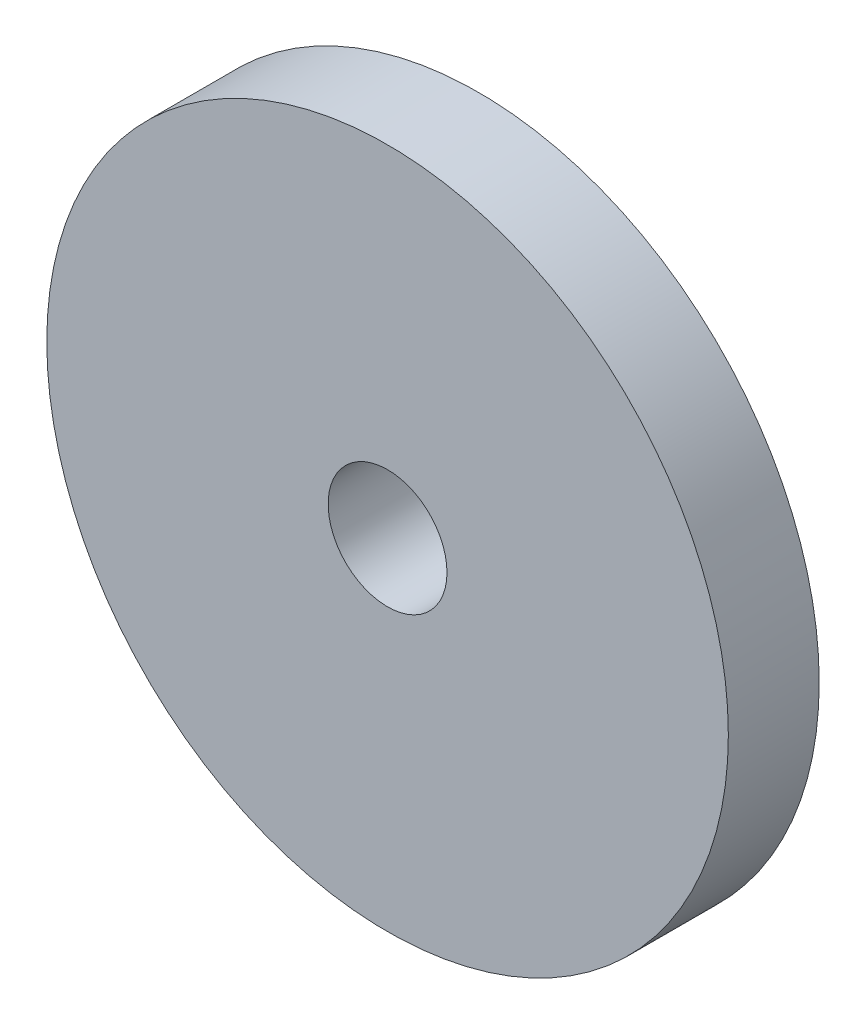
SolidWorks part; units mm, degrees
ref_plane "前视基准面" through (0, 0, 0) normal (0, 0, 1) x (1, 0, 0)
ref_plane "上视基准面" through (0, 0, 0) normal (0, 1, 0) x (1, 0, 0)
ref_plane "右视基准面" through (0, 0, 0) normal (1, 0, 0) x (0, 0, -1)
sketch "草图1" plane through (0, 0, 0) normal (0, 0, 1) x (1, 0, 0)
  circle A0 centre (0, 0) radius 150
  circle A1 centre (0, 0) radius 75
  circle A2 centre (0, 0) radius 38.1
  dimension "D" = 300
  dimension "P" = 150
  dimension "H" = 76.2
sketch "草图2" plane through (0, 0, 0) normal (0, 1, 0) x (1, 0, 0)
  line L0 (0, 11.2412) -> (0, -69.6952) construction
  point P3 (0, -40)
  point P4 (0, -20)
  dimension "F" = 20
  dimension "T" = 40
extrude "凸台-拉伸1" add sketch "草图1" along normal up to vertex (40 mm away) contours A0 A1 | A1 A2 region at (-145.7574, 0, 0) region at (-72.8787, 0, 0) up to point (0, 0, 40)
extrude "切除-拉伸1" cut sketch "草图1<4>" along normal up to vertex (20 mm away) contours A1 A2 region at (-72.8787, 0, 0) up to point (0, 0, 20)
sketch "草图1<4>" plane through (0, 0, 0) normal (0, 0, 1) x (1, 0, 0) same geometry as "草图1"
fillet "圆角1" radius 3.2 1 edges at (75, 0, 20)
scale "缩放比例1" scale about centroid uniform scaling yes scale factor 0.4
sketch "草图3" plane through (0, 0, 28.6598) normal (0, 0, 1) x (1, 0, 0)
  circle A0 centre (0, 0) radius 10.4619
  circle A1 centre (0, 0) radius 15.8137
extrude "凸台-拉伸2" add sketch "草图3" against normal up to surface (16 mm away) up to face at (60, 0, 12.6598)
